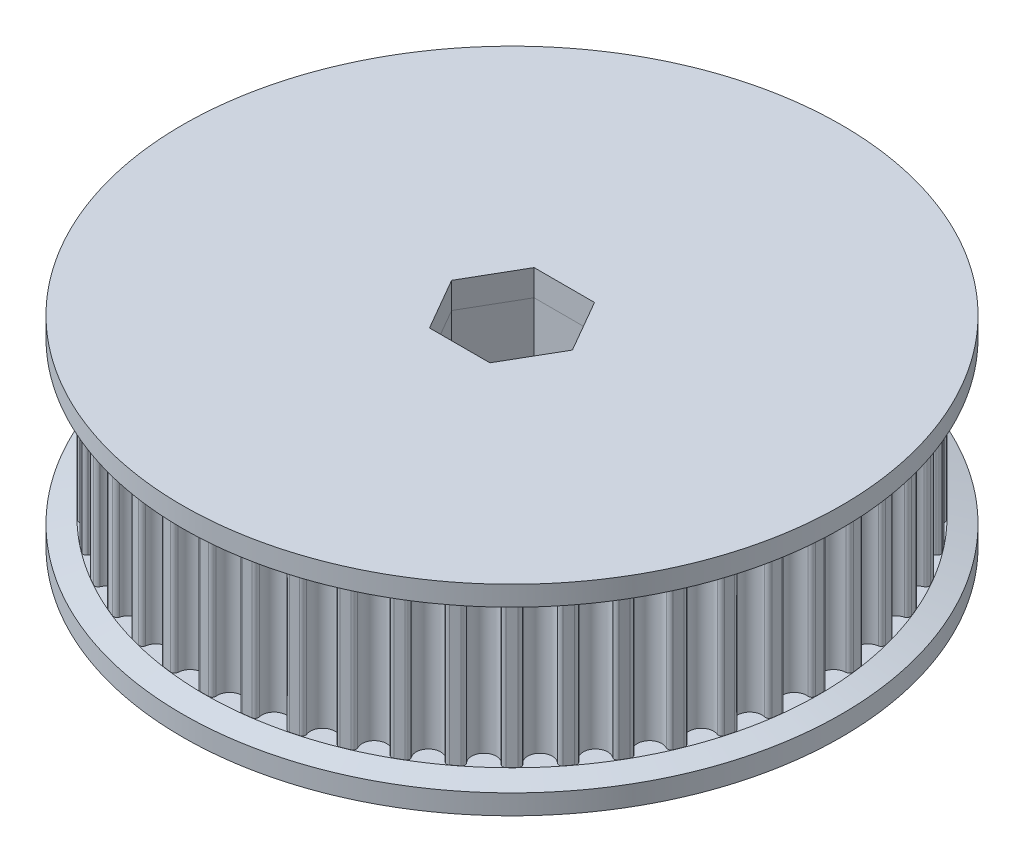
SolidWorks part; units mm, degrees
material "Custom Plastic"
ref_plane "Front Plane" through (0, 0, 0) normal (0, 0, 1) x (1, 0, 0)
ref_plane "Top Plane" through (0, 0, 0) normal (0, 1, 0) x (1, 0, 0)
ref_plane "Right Plane" through (0, 0, 0) normal (1, 0, 0) x (0, 0, -1)
sketch "Sketch1" plane through (0, 0, 0) normal (0, 1, 0) x (1, 0, 0)
  line L0 (0, 34.925) -> (0, 0) construction
  line L2 (7.3323, 0) -> (3.6662, 6.35)
  line L3 (3.6662, 6.35) -> (-3.6662, 6.35)
  line L4 (-3.6662, 6.35) -> (-7.3323, 0)
  line L5 (-7.3323, 0) -> (-3.6662, -6.35)
  line L6 (-3.6662, -6.35) -> (3.6662, -6.35)
  line L7 (3.6662, -6.35) -> (7.3323, 0)
  circle A0 centre (0, 0) radius 34.925 construction
  circle A7 centre (0, 0) radius 38.1972
  circle A9 centre (0, 0) radius 6.35 construction
  point P17 (0, 0)
  dimension "D1" = 12.7
  dimension "D2" = 69.85
  dimension "D7" = 76.3944
extrude "Boss-Extrude1" add sketch "Sketch1" along normal blind 21.175
sketch "Sketch2" plane through (0, 21.175, 0) normal (0, 1, 0) x (1, 0, 0)
  line L0 (0, 0) -> (0, 38.1972) construction
  line L1 (0, -55) -> (0, 55) construction
  line L2 (3.6742, 37.1972) -> (3.75, 37.1972)
  line L3 (-3.75, 37.1972) -> (-3.6742, 37.1972)
  line L4 (-3.75, 37.1972) -> (-3.75, 39.1972)
  line L5 (-3.75, 39.1972) -> (3.75, 39.1972)
  line L6 (3.75, 37.1972) -> (3.75, 39.1972)
  line L7 (-3.75, 37.1972) -> (3.75, 39.1972) construction
  line L8 (-3.75, 39.1972) -> (3.75, 37.1972) construction
  line L9 (-1.199, 34.4472) -> (1.199, 34.4472)
  circle A0 centre (0, 0) radius 38.1972 construction
  arc A1 (-2.9394, 36.5972) -> (-1.199, 34.4472) centre (0, 37.1972) ccw
  arc A2 (1.199, 34.4472) -> (2.9394, 36.5972) centre (0, 37.1972) ccw
  arc A3 (2.9394, 36.5972) -> (3.6742, 37.1972) centre (3.6742, 36.4472) cw
  arc A4 (-2.9394, 36.5972) -> (-3.6742, 37.1972) centre (-3.6742, 36.4472) ccw
  point P10 (0, 38.1972)
  point P19 (3, 37.1972)
  dimension "D3" = 6
  dimension "D5" = 0.75
  dimension "D1" = 2
  dimension "D2" = 7.5
  dimension "D4" = 2.75
extrude "Cut-Extrude1" [suppressed] cut sketch "Sketch2" against normal through all
pattern_circular "CirPattern2" [suppressed] count 153 every 2.353 of bodies 102
sketch "Sketch5" plane through (0, 0, 0) normal (0, 1, 0) x (1, 0, 0)
  line L3 (0, 0) -> (0, 37.3272) construction
  line L4 (0, -55) -> (0, 55) construction
  line L6 (0, 0) -> (2.4982, 38.1154) construction
  line L8 (5.1163, 38.8618) -> (4.8722, 37.0078)
  line L9 (0, 39.1972) -> (0, 37.3272)
  arc A2 (0, 38.1972) -> (4.9857, 37.8704) centre (0, 0) cw construction
  arc A8 (0, 37.3272) -> (0.5019, 37.3238) centre (0, 0) cw
  arc A9 (0.9234, 36.8456) -> (0.5019, 37.3238) centre (0.4962, 36.8939) ccw
  arc A12 (0.9234, 36.8456) -> (3.8938, 36.6509) centre (2.404, 36.6785) ccw
  circle A14 centre (0, 0) radius 38.1972 construction
  arc A15 (3.8938, 36.6509) -> (4.3741, 37.07) centre (4.3237, 36.643) cw
  arc A16 (4.8722, 37.0078) -> (4.3741, 37.07) centre (0, 0) ccw
  arc A17 (0, 39.1972) -> (5.1163, 38.8618) centre (0, 0) cw
  dimension "D1" = 0.43
  dimension "D2" = 1.49
  dimension "D4" = 2.93
  dimension "D5" = 3.75
  dimension "D3" = 0.87
  dimension "D6" = 1
extrude "Cut-Extrude3" cut sketch "Sketch5" along normal up to surface (21.175 mm away) from offset 3.175 contours A17 L9 A8 A9 A12 A15 A16 L8 region at (2.4587, 0, -37.5126) up to face at (0, 21.175, 38.1972)
pattern_circular "CirPattern4" count 48 over 360 about axis through (0, 21.175, 0) along (0, -1, 0) of "Cut-Extrude3"
sketch "Sketch7" plane through (0, 0, 0) normal (0, 1, 0) x (1, 0, 0)
  line L0 (0, 0) -> (-2.553, 167.1573) construction
  line L1 (0, 0) -> (2.553, 167.1573) construction
  line L2 (2.553, 167.1573) -> (-2.553, 167.1573) construction
  line L3 (0, -11.6463) -> (0, 11.6463) construction
  line L5 (-0.625, 167.1573) -> (0.625, 167.1573)
  line L6 (1.4189, 165.7383) -> (0.625, 167.1573) construction
  line L7 (-1.4189, 165.7383) -> (-1.7569, 164.1479) construction
  line L8 (-1.4189, 165.7383) -> (-0.625, 167.1573) construction
  line L9 (1.4189, 165.7383) -> (1.7569, 164.1479) construction
  line L10 (-2.5069, 164.1381) -> (-0.5833, 38.1927)
  line L12 (2.5069, 164.1381) -> (0.5833, 38.1927)
  circle A3 centre (0, 0) radius 165.7444 construction
  arc A4 (-0.625, 167.1573) -> (-1.7569, 164.1479) centre (3.6624, 163.8271) ccw
  arc A5 (0.625, 167.1573) -> (1.7569, 164.1479) centre (-3.6624, 163.8271) cw
  arc A6 (-1.7569, 164.1479) -> (-2.5069, 164.1381) centre (0, 0) ccw
  arc A7 (2.5069, 164.1381) -> (1.7569, 164.1479) centre (0, 0) ccw
  circle A8 centre (0, 0) radius 38.1972 construction
  arc A9 (2.5069, 164.1381) -> (1.7569, 164.1479) centre (0, 0) ccw
  arc A10 (-0.5833, 38.1927) -> (0.5833, 38.1927) centre (0, 0) cw
  arc A11 (-1.7569, 164.1479) -> (-2.5069, 164.1381) centre (0, 0) ccw
  point P4 (0, 167.1573)
  point P14 (0, 167.1573)
  point P22 (-1.4189, 165.7383)
  dimension "D2" = 1.25
  dimension "D4" = 331.4887
  dimension "D5" = 164.1573
  dimension "D1" = 1.75
  dimension "D3" = 0.75
  dimension "D6" = 12
  dimension "D7" = 3
extrude "Boss-Extrude2" [suppressed] add sketch "Sketch7" along normal blind 3.175
pattern_circular "CirPattern5" [suppressed] count 206 over 360 of bodies 109
sketch "Sketch8" plane through (0, 0, 0) normal (0, 1, 0) x (1, 0, 0)
  line L1 (7.3323, 0) -> (3.6662, 6.35)
  line L2 (3.6662, 6.35) -> (-3.6662, 6.35)
  line L3 (-3.6662, 6.35) -> (-7.3323, 0)
  line L4 (-7.3323, 0) -> (-3.6662, -6.35)
  line L5 (-3.6662, -6.35) -> (3.6662, -6.35)
  line L6 (3.6662, -6.35) -> (7.3323, 0)
  circle A1 centre (0, 0) radius 40.005
  circle A2 centre (0, 0) radius 6.35 construction
  dimension "D1" = 80.01
  dimension "D2" = 12.7
extrude "Boss-Extrude3" add sketch "Sketch8" along normal up to surface (3.175 mm away) up to face at (0, 3.175, 0)
extrude "Boss-Extrude4" add sketch "Sketch8<2>" along normal blind 3.175 from surface separate body starting at face at (0, 21.175, 0)
sketch "Sketch8<2>" plane through (0, 0, 0) normal (0, 1, 0) x (1, 0, 0) same geometry as "Sketch8"
chamfer "Chamfer1" distance 0.762 angle 74 1 edges at (0, 3.175, 40.005) first distance on face at (0, 0, 40.005)
chamfer "Chamfer2" distance 0.762 angle 74 1 edges at (0, 21.175, 40.005) first distance on face at (0, 24.35, 40.005)
